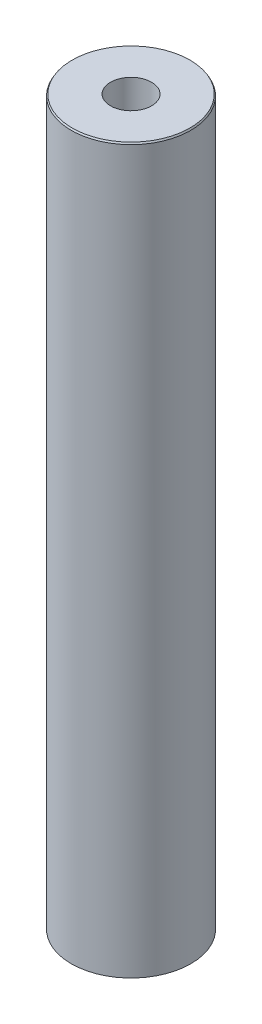
SolidWorks part; units mm, degrees
ref_plane "Front Plane" through (0, 0, 0) normal (0, 0, 1) x (1, 0, 0)
ref_plane "Top Plane" through (0, 0, 0) normal (0, 1, 0) x (1, 0, 0)
ref_plane "Right Plane" through (0, 0, 0) normal (1, 0, 0) x (0, 0, -1)
sketch "Sketch1" plane through (0, 0, 0) normal (0, 1, 0) x (1, 0, 0)
  circle A0 centre (0, 0) radius 32.5
  dimension "SHAFT_OD" = 65
extrude "Boss-Extrude1" add sketch "Sketch1" along normal blind 393.6077
sketch "Sketch2" plane through (0, 0, 0) normal (0, 1, 0) x (1, 0, 0)
  circle A0 centre (0, 0) radius 11.1477
  dimension "BORE_D" = 22.2954
extrude "Cut-Extrude1" cut sketch "Sketch2" along normal through all
chamfer "Chamfer1" distance 0.8565 angle 30 2 edges at (0, 393.6077, 32.5) (0, 0, 32.5) first distance on face at (0, 393.6077, 32.5) first distance on face at (0, 0, 11.1477)
